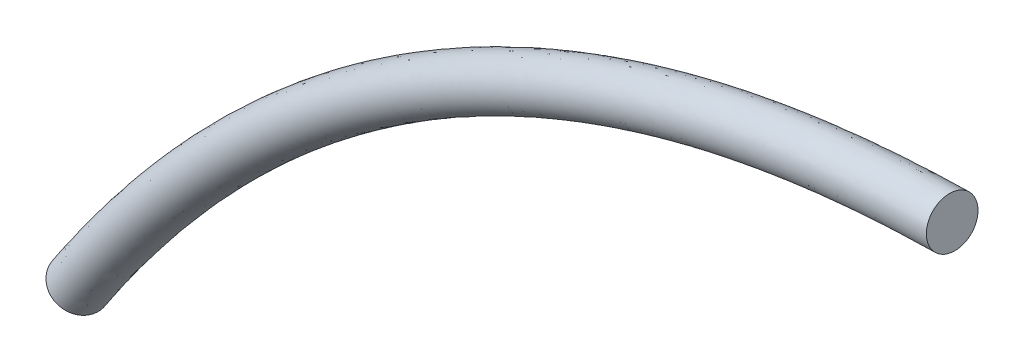
SolidWorks part; units mm, degrees
material "Custom Plastic"
ref_plane "X-Y Datum" through (0, 0, 0) normal (0, 0, 1) x (1, 0, 0)
ref_plane "X-Z Datum" through (0, 0, 0) normal (0, 1, 0) x (1, 0, 0)
ref_plane "Y-Z Datum" through (0, 0, 0) normal (1, 0, 0) x (0, 0, -1)
sketch3d "3DSketch1"
  circle A0 centre (-244.2256, -166.5107, 163.3218) radius 2.9 construction
  circle A1 centre (-70.1324, -53.4906, 183.2483) radius 2.5781 construction
  circle A3 centre (-244.2256, -166.5107, 163.3218) radius 3.475 construction
  spline S0 degree 2 poles (-244.2256, -166.5107, 163.3218) (-168.0574, -59.5751, 178.3266) (-56.5066, -52.2024, 183.9814) knots 0 0 0 1 1 1
  point P0 (-244.2256, -166.5107, 163.3218)
  point P1 (-70.1324, -53.4906, 183.2483)
  point P4 (-246.0339, -168.7779, 163.3218)
  point P8 (-72.6964, -53.7601, 183.2483)
  point P16 (-246.3925, -169.2274, 163.3218)
sweep "Sweep1" add path "3DSketch1" circular profile diameter 9.398 parameters "D3"=9.398
